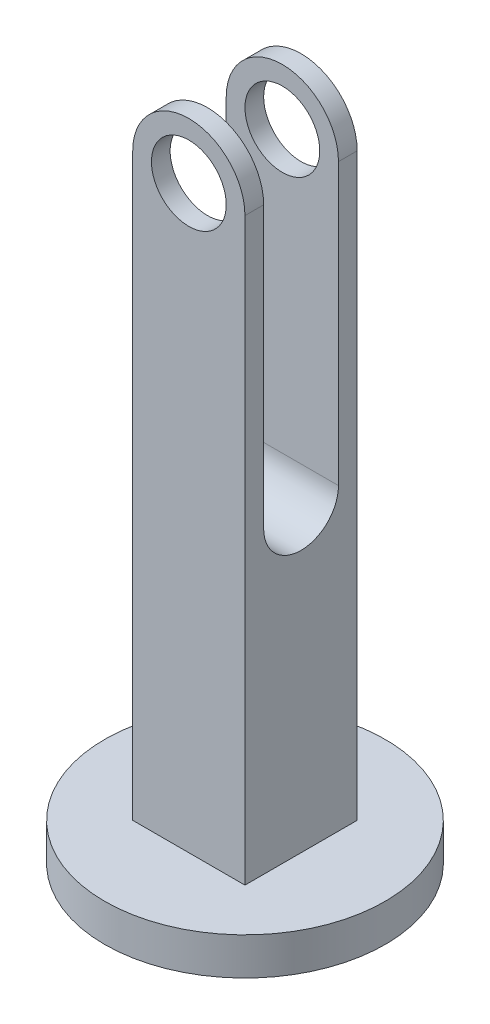
SolidWorks part; units mm, degrees
ref_plane "Front Plane" through (0, 0, 0) normal (0, 0, 1) x (1, 0, 0)
ref_plane "Top Plane" through (0, 0, 0) normal (0, 1, 0) x (1, 0, 0)
ref_plane "Right Plane" through (0, 0, 0) normal (1, 0, 0) x (0, 0, -1)
sketch "Sketch1" plane through (0, 0, 0) normal (0, 1, 0) x (1, 0, 0)
  line L1 (-30, -30) -> (30, -30)
  line L2 (-30, -30) -> (-30, 30)
  line L3 (-30, 30) -> (30, 30)
  line L4 (30, -30) -> (30, 30)
  line L5 (-30, -30) -> (30, 30) construction
  line L6 (-30, 30) -> (30, -30) construction
  circle A0 centre (0, 0) radius 75
  dimension "D1" = 150
  dimension "D2" = 60
  dimension "D3" = 60
extrude "Boss-Extrude1" add sketch "Sketch1" along normal blind 20
extrude "Boss-Extrude2" add sketch "Sketch1<2>" along normal blind 360 contours L1 L4 L3 L2 region at (0, 0, 0)
sketch "Sketch1<2>" plane through (0, 0, 0) normal (0, 1, 0) x (1, 0, 0) same geometry as "Sketch1"
sketch "Sketch2" plane through (30, 0, 0) normal (1, 0, 0) x (0, 0, -1)
  line L0 (-20, 360) -> (20, 360)
  line L1 (-20, 360) -> (-20, 180)
  line L2 (20, 360) -> (20, 180)
  line L4 (-30, 360) -> (30, 360) construction
  line L5 (30, 360) -> (30, 20) construction
  line L6 (-30, 360) -> (-30, 20) construction
  arc A0 (-20, 180) -> (20, 180) centre (0, 180) ccw
  dimension "D1" = 10
  dimension "D2" = 10
extrude "Cut-Extrude1" cut sketch "Sketch2" against normal through all
sketch "Sketch3" plane through (0, 0, 30) normal (0, 0, 1) x (1, 0, 0)
  line L0 (-30, 360) -> (-30, 20) construction
  line L1 (30, 360) -> (30, 20) construction
  line L2 (-30, 360) -> (30, 360) construction
  line L7 (-30, 20) -> (30, 20)
  line L8 (30, 20) -> (30, 360)
  line L9 (30, 360) -> (-30, 360)
  line L10 (-30, 360) -> (-30, 20)
  line L12 (30, 330) -> (30, 360)
  line L13 (30, 360) -> (-30, 360)
  line L14 (-30, 360) -> (-30, 330)
  arc A0 (-30, 330) -> (30, 330) centre (0, 330) cw
  circle A1 centre (0, 330) radius 20
  line M6 (30, 20) -> (30, 360)
  line M7 (30, 360) -> (-30, 360)
  line M8 (-30, 360) -> (-30, 20)
  dimension "D2" = 40
  dimension "D1" = 0
extrude "Cut-Extrude2" cut sketch "Sketch3" against normal through all contours A1 | A0 M7 M6 | A0 L13 M8 region at (-23.299, 353.299, 30) region at (23.299, 353.299, 30) region at (0, 330, 30)
